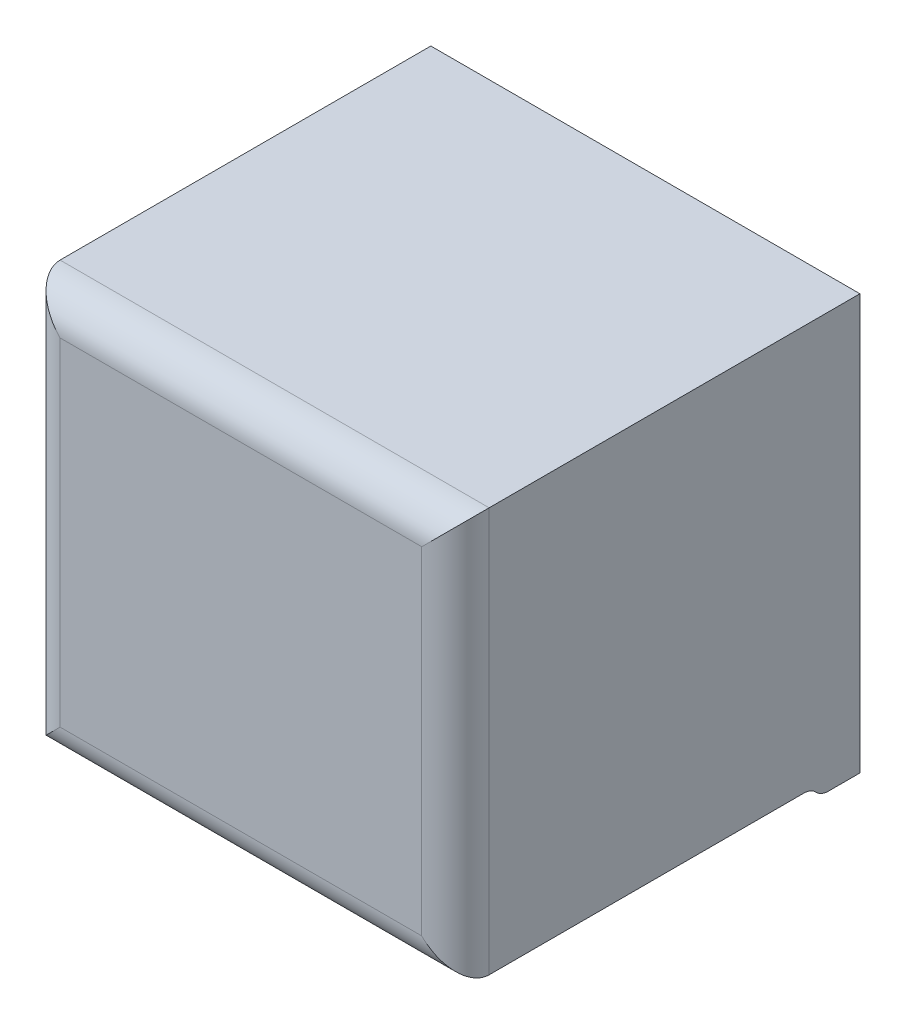
SolidWorks part; units mm, degrees
ref_plane "Front Plane" through (0, 0, 0) normal (0, 0, 1) x (1, 0, 0)
ref_plane "Top Plane" through (0, 0, 0) normal (0, 1, 0) x (1, 0, 0)
ref_plane "Right Plane" through (0, 0, 0) normal (1, 0, 0) x (0, 0, -1)
sketch "Sketch1" plane through (0, 0, 0) normal (0, 0, 1) x (1, 0, 0)
  line L0 (0, 0) -> (-127.3, 0)
  line L1 (-127.3, 0) -> (-127.3, -120)
  line L2 (-127.3, -120) -> (0, -120)
  line L3 (0, -120) -> (0, 0)
  dimension "D1" = 127.3
  dimension "D2" = 120
extrude "Boss-Extrude1" add sketch "Sketch1" along normal blind 120
fillet "Fillet1" radius 10 4 edges at (-63.65, -120, 120) (-63.65, 0, 120) (0, -60, 120) (-127.3, -60, 120)
sketch "Sketch2" plane through (0, 0, 0) normal (0, 0, -1) x (-1, 0, 0)
  line L0 (0, -60) -> (127.3, -60) construction
  line L1 (0, -120) -> (0, 0) construction
  line L2 (127.3, 0) -> (127.3, -120) construction
  line L3 (63.65, 0) -> (63.65, -120) construction
  line L4 (0, 0) -> (127.3, 0) construction
  line L5 (127.3, -120) -> (0, -120) construction
  line L6 (0, -10) -> (10, -10)
  line L7 (127.3, -120) -> (0, -120)
  line L8 (127.3, -120) -> (127.3, 0)
  line L9 (127.3, 0) -> (0, 0)
  line L10 (0, -120) -> (0, 0)
  line L11 (127.3, -120) -> (0, 0) construction
  line L12 (127.3, 0) -> (0, -120) construction
  line L13 (10, -10) -> (10, 0)
  line L14 (117.3, -10) -> (117.3, 0)
  line L15 (127.3, -10) -> (117.3, -10)
  line L16 (127.3, -110) -> (117.3, -110)
  line L17 (117.3, -110) -> (117.3, -120)
  line L18 (0, -110) -> (10, -110)
  line L19 (10, -110) -> (10, -120)
  circle A0 centre (5, -4.7133) radius 1.7
  circle A1 centre (122.3, -4.7133) radius 1.7
  circle A2 centre (122.3, -115.2867) radius 1.7
  circle A3 centre (5, -115.2867) radius 1.7
  point P12 (63.65, -60)
  dimension "D5" = 3.4
  dimension "D1" = 5
  dimension "D2" = 5
  dimension "D3" = 5
  dimension "D4" = 5
  dimension "D6" = 10
  dimension "D7" = 10
shell "Shell3" thickness 5 removed face at (-63.65, -60, 0)
sketch "Sketch3" plane through (0, 0, 0) normal (0, 0, -1) x (-1, 0, 0)
  line L0 (10, -110) -> (10, -120) construction
  line L1 (0, -110) -> (10, -110) construction
  line L2 (117.3, -110) -> (117.3, -120) construction
  line L3 (127.3, -110) -> (117.3, -110) construction
  line L4 (127.3, -10) -> (117.3, -10) construction
  line L5 (117.3, -10) -> (117.3, 0) construction
  line L6 (10, -10) -> (10, 0) construction
  line L7 (0, -10) -> (10, -10) construction
  line L8 (10, -110) -> (10, -120)
  line L9 (0, -110) -> (10, -110)
  line L10 (117.3, -110) -> (117.3, -120)
  line L11 (127.3, -110) -> (117.3, -110)
  line L12 (127.3, -10) -> (117.3, -10)
  line L13 (117.3, -10) -> (117.3, 0)
  line L14 (10, -10) -> (10, 0)
  line L15 (0, -10) -> (10, -10)
  line L16 (0, -10) -> (0, 0)
  line L17 (0, 0) -> (10, 0)
  line L18 (117.3, 0) -> (127.3, 0)
  line L19 (127.3, 0) -> (127.3, -10)
  line L20 (127.3, -110) -> (127.3, -120)
  line L21 (127.3, -120) -> (117.3, -120)
  line L22 (0, -110) -> (0, -120)
  line L23 (0, -120) -> (10, -120)
  circle A0 centre (122.3, -115.2867) radius 1.7 construction
  circle A1 centre (5, -115.2867) radius 1.7 construction
  circle A2 centre (122.3, -4.7133) radius 1.7 construction
  circle A3 centre (5, -4.7133) radius 1.7 construction
  circle A4 centre (122.3, -115.2867) radius 1.7
  circle A5 centre (5, -115.2867) radius 1.7
  circle A6 centre (122.3, -4.7133) radius 1.7
  circle A7 centre (5, -4.7133) radius 1.7
extrude "Boss-Extrude3" add sketch "Sketch3" against normal blind 20
extrude "Cut-Extrude1" cut sketch "Sketch2" against normal blind 20 and the other way through all contours A2 | A3 | A1 | A0 region at (-5, -4.7133, 0) region at (-122.3, -4.7133, 0) region at (-122.3, -115.2867, 0) region at (-5, -115.2867, 0)
fillet "Fillet5" radius 5 4 edges at (-117.3, -110, 10) (-10, -110, 10) (-117.3, -10, 10) (-10, -10, 10)
sketch "Sketch4" plane through (0, -120, 0) normal (0, -1, 0) x (1, 0, 0)
  line L0 (-127.3, 110) -> (-127.3, 0) construction
  line L1 (-116.3, 13) -> (-104.3, 13)
  line L2 (-116.3, 13) -> (-116.3, 25)
  line L3 (-116.3, 25) -> (-104.3, 25)
  line L4 (-104.3, 13) -> (-104.3, 25)
  line L5 (-116.3, 13) -> (-104.3, 25) construction
  line L6 (-116.3, 25) -> (-104.3, 13) construction
  line L7 (-127.3, 0) -> (0, 0) construction
  point P0 (-110.3, 19)
  dimension "D1" = 12
  dimension "D2" = 12
  dimension "D3" = 17
  dimension "D4" = 19
extrude "Cut-Extrude2" cut sketch "Sketch4" against normal blind 11
sketch "Sketch5" plane through (0, -120, 0) normal (0, -1, 0) x (1, 0, 0)
  line L0 (-127.3, 0) -> (-127.3, 12)
  line L1 (-127.3, 110) -> (-127.3, 0) construction
  line L2 (-127.3, 12) -> (0, 12)
  line L3 (0, 110) -> (0, 0) construction
  line L4 (0, 12) -> (0, 0)
  line L5 (-127.3, 0) -> (0, 0)
  dimension "D1" = 12
extrude "Boss-Extrude4" add sketch "Sketch5" along normal blind 3.14
fillet "Fillet6" radius 5 1 edges at (-63.65, -120, 12)
fillet "Fillet7" radius 5 1 edges at (-63.65, -123.14, 12)
sketch "Sketch6" plane through (0, -123.14, 0) normal (0, -1, 0) x (1, 0, 0)
  line L0 (-127.3, 0) -> (0, 0) construction
  line L1 (-73.65, 0) -> (-53.65, 0)
  line L2 (-73.65, 5) -> (-73.65, 30)
  line L3 (-68.65, 35) -> (-58.65, 35)
  line L4 (-53.65, 5) -> (-53.65, 30)
  line L5 (-78.65, 0) -> (-127.3, 0)
  line L6 (-48.65, 0) -> (0, 0)
  line L7 (0, 110) -> (0, 16.6412) construction
  line L8 (-53.4, 5) -> (-53.4, 30)
  line L9 (-68.65, 35.25) -> (-58.65, 35.25)
  line L10 (-73.9, 5) -> (-73.9, 30)
  line L11 (-78.65, 0.25) -> (-78.65, 0)
  line L12 (-78.65, 0) -> (-48.65, 0)
  line L13 (-48.65, 0) -> (-48.65, 0.25)
  arc A0 (-58.65, 35) -> (-53.65, 30) centre (-58.65, 30) cw
  arc A1 (-73.65, 30) -> (-68.65, 35) centre (-68.65, 30) cw
  arc A2 (-73.65, 5) -> (-78.65, 0) centre (-78.65, 5) cw
  arc A3 (-53.65, 5) -> (-48.65, 0) centre (-48.65, 5) ccw
  arc A4 (-53.4, 5) -> (-48.65, 0.25) centre (-48.65, 5) ccw
  arc A5 (-58.65, 35.25) -> (-53.4, 30) centre (-58.65, 30) cw
  arc A6 (-73.9, 30) -> (-68.65, 35.25) centre (-68.65, 30) cw
  arc A7 (-73.9, 5) -> (-78.65, 0.25) centre (-78.65, 5) cw
  point P8 (-53.65, 35)
  point P11 (-73.65, 35)
  line M9 (0, 9.3651) -> (-127.3, 9.3651)
  line M11 (-127.3, 0) -> (0, 0)
  dimension "D3" = 5
  dimension "D4" = 5
  dimension "D5" = 5
  dimension "D1" = 20
  dimension "D2" = 35
  dimension "D6" = 53.65
  dimension "D7" = 0.25
extrude "Cut-Extrude3" cut sketch "Sketch6" against normal blind 13.14 contours A3 L4 L2 A2 M9 M11 | A1 L2 L4 A0 L3 M9 | A6 L10 L2 A1 L3 A0 L4 L8 A5 L9 M9 | A4 L8 L4 A3 L13 M9 | L10 A7 L11 A2 L2 M9 region at (-63.65, -123.14, 4.4894) region at (-78.5438, -123.14, 0.125) region at (-52.1105, -123.14, 1.5395) region at (-73.775, -123.14, 9.6953) region at (-63.65, -123.14, 21.9325)
sketch "Sketch7" plane through (0, -120, 0) normal (0, -1, 0) x (1, 0, 0)
  line L0 (-63.65, 35.25) -> (-63.65, 29.25) construction
  line L1 (-58.65, 35.25) -> (-68.65, 35.25) construction
  line L2 (-83.65, 29.25) -> (-83.65, 23.25) construction
  line L3 (-83.65, 23.25) -> (-43.65, 23.25) construction
  line L4 (-43.65, 23.25) -> (-43.65, 29.25) construction
  line L5 (-43.65, 29.25) -> (-83.65, 29.25) construction
  line L6 (-83.65, 26.25) -> (-43.65, 26.25) construction
  circle A0 centre (-83.65, 29.25) radius 1.7
  circle A1 centre (-83.65, 23.25) radius 1.7
  circle A2 centre (-43.65, 23.25) radius 1.7
  circle A3 centre (-43.65, 29.25) radius 1.7
  dimension "D1" = 3.4
  dimension "D2" = 3.4
  dimension "D3" = 6
  dimension "D4" = 40
  dimension "D5" = 6
extrude "Cut-Extrude4" [suppressed] cut sketch "Sketch7" against normal blind 13.14 contours A0 | A1 | A3 | A2
